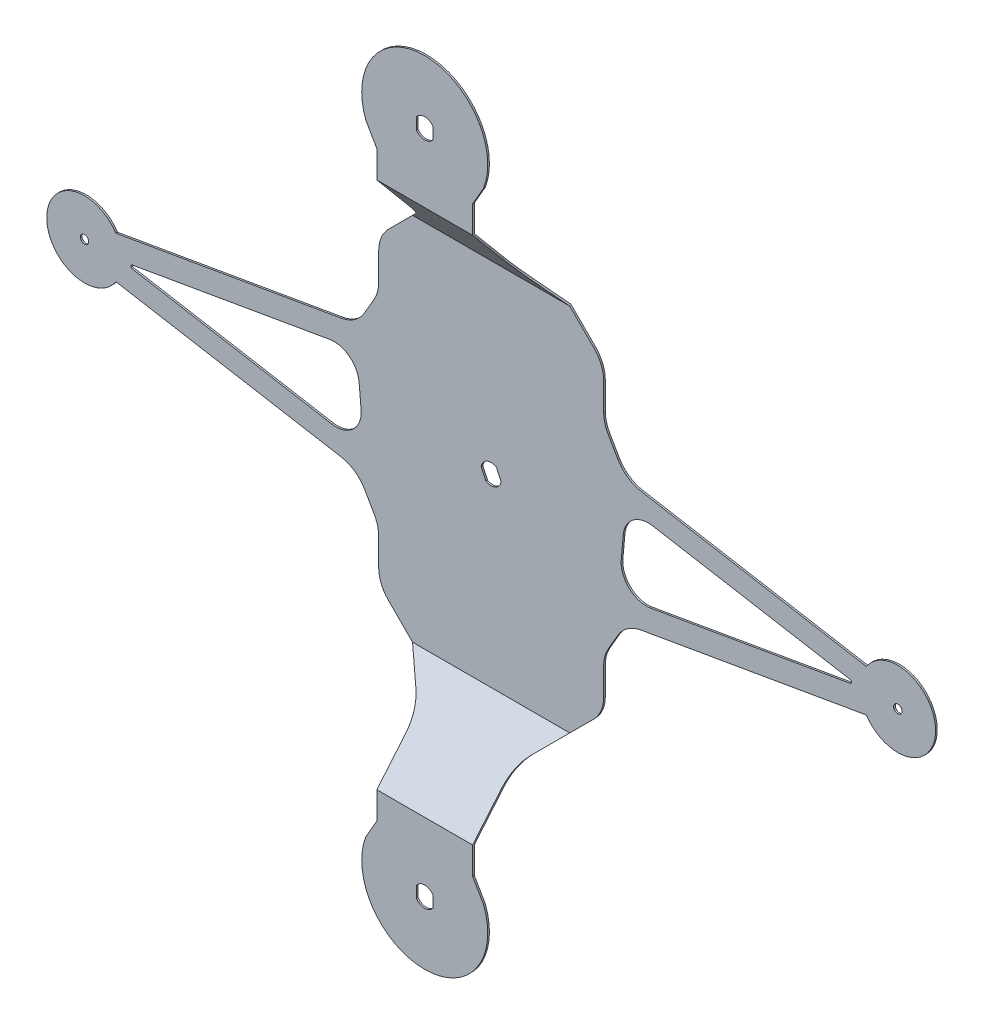
SolidWorks part; units mm, degrees
ref_plane "Alzado" through (0, 0, 0) normal (0, 0, 1) x (1, 0, 0)
ref_plane "Planta" through (0, 0, 0) normal (0, 1, 0) x (1, 0, 0)
ref_plane "Vista lateral" through (0, 0, 0) normal (1, 0, 0) x (0, 0, -1)
sketch "Croquis1" plane through (0, 0, 0) normal (1, 0, 0) x (0, 0, -1)
  line L0 (-18.5, -110) -> (-18.5, 110)
  line L1 (-18.5, 110) -> (-58.0314, 157.1117)
  line L2 (0, 0) -> (-82.8072, 0) construction
  line L3 (-58.0314, 157.1117) -> (-58.0314, 248)
  line L4 (-18.5, -110) -> (-58.0314, -157.1117)
  line L5 (-58.0314, -157.1117) -> (-58.0314, -248)
  line L6 (-57.0314, -157.4757) -> (-57.0314, -248)
  line L7 (-17.5, -110.364) -> (-57.0314, -157.4757)
  line L8 (-17.5, -110.364) -> (-17.5, 110.364)
  line L9 (-17.5, 110.364) -> (-57.0314, 157.4757)
  line L10 (-57.0314, 157.4757) -> (-57.0314, 248)
  line L11 (-58.0314, 248) -> (-57.0314, 248)
  line L12 (-58.0314, -248) -> (-57.0314, -248)
  point P9 (-18.5, 0)
  dimension "D1" = 18.5
  dimension "D2" = 50
  dimension "D3" = 61.5
  dimension "D4" = 110
  dimension "D5" = 496
  dimension "D6" = 1
extrude "Saliente-Extruir1" add sketch "Croquis1" along normal mid plane 542
sketch "Croquis2" plane through (0, 0, 0) normal (0, 0, 1) x (1, 0, 0)
  line L1 (0, 277.0309) -> (0, -277.0309) construction
  line L7 (-223.2917, 12.5) -> (-48.4123, 12.5) construction
  line L9 (-300.4496, 0) -> (300.4496, 0) construction
  line L10 (-223.2917, -12.5) -> (-48.4123, -12.5) construction
  line L11 (-28.5, 173.2788) -> (-28.5, 128.2788)
  line L12 (-28.5, 173.2788) -> (-35, 184.5371)
  line L13 (-28.5, 128.2788) -> (-66.9394, 89.8394)
  line L14 (-66.9394, 89.8394) -> (-66.9394, 60)
  line L15 (-66.9394, 60) -> (-80, 37.3784)
  line L16 (35, 184.5371) -> (-35, 184.5371) construction
  line L17 (35, 184.5371) -> (35, 211.4629) construction
  line L18 (35, 211.4629) -> (-35, 211.4629) construction
  line L19 (-35, 184.5371) -> (-35, 211.4629) construction
  line L31 (35, 184.5371) -> (-35, 211.4629) construction
  line L33 (35, 211.4629) -> (-35, 184.5371) construction
  line L34 (-80, 37.3784) -> (-223.2917, 12.5)
  line L36 (-219.2917, 0) -> (-80, 24.1839)
  line L37 (-219.2917, 0) -> (-80, -24.1839)
  line L38 (-28.5, -173.2788) -> (-35, -184.5371)
  line L39 (-28.5, -173.2788) -> (-28.5, -128.2788)
  line L40 (-28.5, -128.2788) -> (-66.9394, -89.8394)
  line L41 (-80, -37.3784) -> (-223.2917, -12.5)
  line L42 (-66.9394, -60) -> (-80, -37.3784)
  line L43 (-66.9394, -89.8394) -> (-66.9394, -60)
  line L44 (-80, 24.1839) -> (-75.7031, -24.9299)
  line L45 (-75.7031, -24.9299) -> (-80, -24.1839)
  line L46 (28.5, 173.2788) -> (35, 184.5371)
  line L47 (28.5, -173.2788) -> (35, -184.5371)
  line L48 (28.5, -173.2788) -> (28.5, -128.2788)
  line L49 (28.5, -128.2788) -> (66.9394, -89.8394)
  line L50 (66.9394, -89.8394) -> (66.9394, -60)
  line L51 (66.9394, -60) -> (80, -37.3784)
  line L52 (80, 24.1839) -> (75.7031, -24.9299)
  line L53 (80, -37.3784) -> (223.2917, -12.5)
  line L54 (219.2917, 0) -> (80, -24.1839)
  line L55 (219.2917, 0) -> (80, 24.1839)
  line L56 (80, 37.3784) -> (223.2917, 12.5)
  line L57 (66.9394, 60) -> (80, 37.3784)
  line L58 (66.9394, 89.8394) -> (66.9394, 60)
  line L59 (28.5, 128.2788) -> (66.9394, 89.8394)
  line L60 (28.5, 173.2788) -> (28.5, 128.2788)
  line L61 (75.7031, -24.9299) -> (80, -24.1839)
  line L62 (-290.79, 277.0309) -> (290.79, 277.0309)
  line L63 (-290.79, 277.0309) -> (-290.79, -277.0309)
  line L64 (-290.79, -277.0309) -> (290.79, -277.0309)
  line L65 (290.79, 277.0309) -> (290.79, -277.0309)
  line L66 (-290.79, 277.0309) -> (290.79, -277.0309) construction
  line L67 (-290.79, -277.0309) -> (290.79, 277.0309) construction
  circle A9 centre (0, 0) radius 247.5 construction
  arc A10 (-223.2917, 12.5) -> (-223.2917, -12.5) centre (-242, 0) ccw
  circle A11 centre (0, 0) radius 50 construction
  arc A12 (-35, 184.5371) -> (35, 184.5371) centre (0, 198) cw
  arc A13 (-35, -184.5371) -> (35, -184.5371) centre (0, -198) ccw
  arc A14 (223.2917, 12.5) -> (223.2917, -12.5) centre (242, 0) cw
  circle A15 centre (0, 198) radius 37.5 construction
  point P6 (0, 0)
  point P7 (0, 0)
  dimension "D1" = 495
  dimension "D3" = 45
  dimension "D9" = 198
  dimension "D4" = 100
  dimension "D6" = 25
  dimension "D10" = 60
  dimension "D14" = 60
  dimension "D5" = 75
  dimension "D2" = 242
  dimension "D7" = 70
  dimension "D8" = 57
  dimension "D11" = 45
  dimension "D12" = 45
  dimension "D13" = 120
  dimension "D15" = 160
  dimension "D16" = 13
  dimension "D17" = 5
  dimension "D18" = 160
  dimension "D19" = 4
sketch "Croquis4" plane through (0, 0, 0) normal (0, 0, 1) x (1, 0, 0)
  line L0 (-326.6263, 0) -> (326.6263, 0) construction
  line L1 (0, 278.5393) -> (0, -278.5393) construction
  line L2 (-5, -194.6834) -> (5, -201.3166) construction
  line L3 (-5, 201.3166) -> (5, 201.3166) construction
  line L4 (-5, 201.3166) -> (-5, 194.6834)
  line L5 (-5, 194.6834) -> (5, 194.6834) construction
  line L6 (5, 201.3166) -> (5, 194.6834)
  line L7 (-5, 201.3166) -> (5, 194.6834) construction
  line L8 (-5, 194.6834) -> (5, 201.3166) construction
  line L9 (-5, -201.3166) -> (5, -194.6834) construction
  line L10 (-5, -194.6834) -> (5, -194.6834) construction
  line L11 (-5, -201.3166) -> (5, -201.3166) construction
  line L12 (5, -201.3166) -> (5, -194.6834)
  line L13 (-5, -201.3166) -> (-5, -194.6834)
  line L26 (-5.9332, 0.8928) -> (3.1299, 5.119) construction
  line L27 (-5.9332, 0.8928) -> (-3.1299, -5.119)
  line L28 (3.1299, 5.119) -> (5.9332, -0.8928)
  line L29 (-3.1299, -5.119) -> (5.9332, -0.8928) construction
  line L30 (0, 0) -> (-1.4017, 3.0059) construction
  arc A0 (-5, 194.6834) -> (5, 194.6834) centre (0, 198) ccw
  arc A1 (-3.1299, -5.119) -> (5.9332, -0.8928) centre (0, 0) ccw
  arc A4 (5, 201.3166) -> (-5, 201.3166) centre (0, 198) ccw
  arc A5 (5, -201.3166) -> (-5, -201.3166) centre (0, -198) cw
  arc A6 (-5, -194.6834) -> (5, -194.6834) centre (0, -198) cw
  circle A7 centre (-242, 0) radius 2.5
  arc A10 (3.1299, 5.119) -> (-5.9332, 0.8928) centre (0, 0) ccw
  circle A11 centre (242, 0) radius 2.5
  point P4 (0, 0)
  point P8 (0, 0)
  dimension "D4" = 10
  dimension "D5" = 12
  dimension "D6" = 12
  dimension "D2" = 5
  dimension "D1" = 198
  dimension "D8" = 10
  dimension "D9" = 25
extrude "Cortar-Extruir9" cut sketch "Croquis4" against normal through all both and the other way through all
extrude "Cortar-Extruir10" cut sketch "Croquis2" against normal through all both and the other way through all contours L65 L62 L63 L64 L56 A14 L53 L51 L50 L49 L48 L47 A13 L38 L39 L40 L43 L42 L41 A10 L34 L15 L14 L13 L11 L12 A12 L46 L60 L59 L58 L57 | L45 L44 L36 L37 | L52 L61 L54 L55 region at (-124.9983, -0.2487, 0) region at (124.9983, -0.2487, 0) region at (0, 268.9983, 0)
fillet "Redondeo1" radius 20 16 edges at (66.9394, -89.8394, 18) (66.9394, -60, 18) (80, -37.3784, 18) (28.5, -128.2788, 33.185) (-28.5, -128.2788, 33.185) (-66.9394, -89.8394, 18) (-66.9394, -60, 18) (-80, -37.3784, 18) (-80, 37.3784, 18) (-66.9394, 60, 18) (-66.9394, 89.8394, 18) (-28.5, 128.2788, 33.185) (80, 37.3784, 18) (66.9394, 60, 18) (66.9394, 89.8394, 18) (28.5, 128.2788, 33.185)
fillet "Redondeo2" radius 15 4 edges at (75.7031, -24.9299, 18) (80, 24.1839, 18) (-75.7031, -24.9299, 18) (-80, 24.1839, 18)
fillet "Redondeo3" radius 1 2 edges at (219.2917, 0, 18) (-219.2917, 0, 18)
